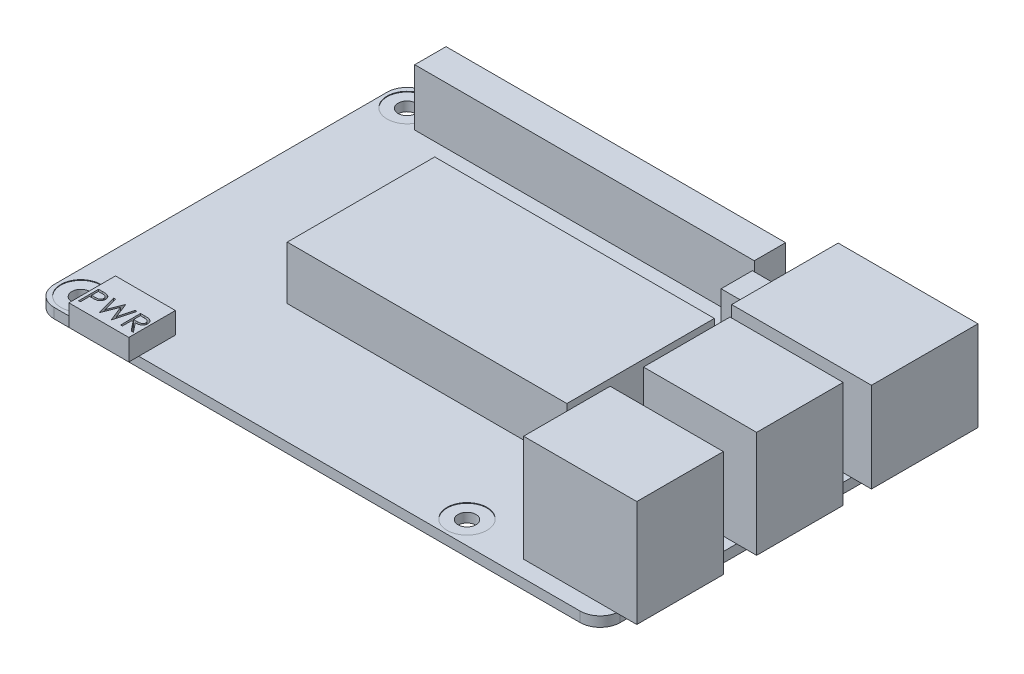
SolidWorks part; units mm, degrees
ref_plane "Front Plane" through (0, 0, 0) normal (0, 0, 1) x (1, 0, 0)
ref_plane "Top Plane" through (0, 0, 0) normal (0, 1, 0) x (1, 0, 0)
ref_plane "Right Plane" through (0, 0, 0) normal (1, 0, 0) x (0, 0, -1)
sketch "Sketch1" plane through (0, 0, 0) normal (0, 1, 0) x (1, 0, 0)
  line L0 (3.5, 52.5) -> (61.5, 52.5) construction
  line L1 (0, 0) -> (85, 0)
  line L2 (0, 0) -> (0, 56)
  line L3 (0, 56) -> (85, 56)
  line L4 (85, 0) -> (85, 56)
  line L5 (61.5, 52.5) -> (61.5, 3.5) construction
  line L6 (61.5, 3.5) -> (3.5, 3.5) construction
  line L7 (3.5, 3.5) -> (3.5, 52.5) construction
  circle A0 centre (3.5, 52.5) radius 1.35
  circle A1 centre (3.5, 3.5) radius 1.35
  circle A2 centre (61.5, 3.5) radius 1.35
  circle A3 centre (61.5, 52.5) radius 1.35
  dimension "D5" = 2.7
  dimension "D6" = 3.5
  dimension "D7" = 3.5
  dimension "D1" = 85
  dimension "D2" = 56
  dimension "D3" = 58
  dimension "D4" = 49
extrude "Boss-Extrude1" add sketch "Sketch1" along normal blind 1.5
fillet "Fillet1" radius 3 4 edges at (85, 0.75, -56) (85, 0.75, 0) (0, 0.75, -56) (0, 0.75, 0)
sketch "Sketch2" plane through (0, 1.5, 0) normal (0, 1, 0) x (1, 0, 0)
  line L0 (3, 0) -> (82, 0) construction
  line L1 (88, 20.5) -> (71, 20.5)
  line L2 (88, 20.5) -> (88, 33.5)
  line L3 (88, 33.5) -> (71, 33.5)
  line L4 (71, 20.5) -> (71, 33.5)
  line L5 (88, 2.5) -> (71, 2.5)
  line L6 (88, 2.5) -> (88, 15.5)
  line L7 (88, 15.5) -> (71, 15.5)
  line L8 (71, 2.5) -> (71, 15.5)
  line L9 (85, 3) -> (85, 53) construction
  point P8 (88, 9)
  point P11 (88, 27)
  dimension "D1" = 17
  dimension "D2" = 13
  dimension "D3" = 9
  dimension "D4" = 27
  dimension "D5" = 3
extrude "Boss-Extrude2" add sketch "Sketch2" along normal blind 16
sketch "Sketch3" plane through (0, 1.5, 0) normal (0, 1, 0) x (1, 0, 0)
  line L0 (88, 20.5) -> (88, 33.5) construction
  line L1 (88, 37.75) -> (67, 37.75)
  line L2 (88, 37.75) -> (88, 53.75)
  line L3 (88, 53.75) -> (67, 53.75)
  line L4 (67, 37.75) -> (67, 53.75)
  line L5 (3, 0) -> (82, 0) construction
  point P6 (88, 45.75)
  dimension "D1" = 21
  dimension "D2" = 16
  dimension "D3" = 45.75
extrude "Boss-Extrude3" add sketch "Sketch3" along normal blind 13.5
sketch "Sketch4" plane through (0, 1.5, 0) normal (0, 1, 0) x (1, 0, 0)
  line L0 (61.5, 52.5) -> (61.5, 48.71) construction
  line L1 (7, 54.85) -> (58, 54.85)
  line L2 (7, 54.85) -> (7, 50.15)
  line L3 (7, 50.15) -> (58, 50.15)
  line L4 (58, 54.85) -> (58, 50.15)
  line L5 (59.15, 48.71) -> (63.85, 48.71)
  line L6 (59.15, 48.71) -> (59.15, 44.01)
  line L7 (59.15, 44.01) -> (63.85, 44.01)
  line L8 (63.85, 48.71) -> (63.85, 44.01)
  line L9 (3.5, 52.5) -> (61.5, 52.5) construction
  point P11 (63.85, 46.36)
  point P13 (32.5, 52.5)
  point P15 (32.5, 54.85)
  point P16 (7, 52.5)
  dimension "D1" = 6.14
  dimension "D2" = 51
  dimension "D3" = 4.7
  dimension "D4" = 4.7
extrude "Boss-Extrude4" add sketch "Sketch4" along normal blind 8.5
sketch "Sketch5" plane through (0, 1.5, 0) normal (0, 1, 0) x (1, 0, 0)
  line L0 (3, 0) -> (82, 0) construction
  line L1 (6.7, -1.5) -> (15.7, -1.5)
  line L2 (6.7, -1.5) -> (6.7, 5.5)
  line L3 (6.7, 5.5) -> (15.7, 5.5)
  line L4 (15.7, -1.5) -> (15.7, 5.5)
  circle A0 centre (3.5, 3.5) radius 1.35 construction
  point P8 (11.2, -1.5)
  dimension "D4" = 7.7
  dimension "D1" = 9
  dimension "D2" = 7
  dimension "D3" = 1.5
extrude "Boss-Extrude5" add sketch "Sketch5" along normal blind 3.2
sketch "Sketch6" plane through (0, 4.7, 0) normal (0, 1, 0) x (1, 0, 0)
  line L0 (6.7, -0.5) -> (15.7, -0.5) construction
  line L1 (6.7, 5.5) -> (6.7, -1.5) construction
  line L2 (15.7, -1.5) -> (15.7, 5.5) construction
  line L3 (6.7, -1.5) -> (15.7, -1.5) construction
  text T0 "PWR" font "Century Gothic" height 3
  dimension "D1" = 1
extrude "Cut-Extrude1" cut sketch "Sketch6" against normal blind 1
sketch "Sketch7" plane through (0, 1.5, 0) normal (0, 1, 0) x (1, 0, 0)
  line L0 (0, 53) -> (0, 3) construction
  line L5 (62, 18) -> (20, 18)
  line L6 (62, 18) -> (62, 40.15)
  line L7 (62, 40.15) -> (20, 40.15)
  line L8 (20, 18) -> (20, 40.15)
  line L9 (67, 53.75) -> (67, 37.75) construction
  line L10 (7, 50.15) -> (58, 50.15) construction
  line L11 (15.7, 0) -> (82, 0) construction
  point P0 (14.4381, 36.9872)
  dimension "D1" = 20
  dimension "D2" = 5
  dimension "D3" = 10
  dimension "D4" = 18
extrude "Boss-Extrude6" add sketch "Sketch7" along normal blind 8
sketch "Sketch8" plane through (0, 10, 0) normal (0, 1, 0) x (1, 0, 0)
  line L0 (7, 52.5) -> (58, 52.5)
  line L1 (7, 54.85) -> (7, 50.15) construction
  line L2 (58, 50.15) -> (58, 54.85) construction
  line L3 (9.5, 54.85) -> (9.5, 50.15)
  line L4 (7, 54.85) -> (58, 54.85)
  line L5 (7, 54.85) -> (7, 50.15)
  line L6 (7, 50.15) -> (58, 50.15)
  line L7 (58, 54.85) -> (58, 50.15)
  line L8 (12, 54.85) -> (12, 50.15)
  line L9 (14.5, 54.85) -> (14.5, 50.15)
  line L10 (17, 54.85) -> (17, 50.15)
  line L11 (19.5, 54.85) -> (19.5, 50.15)
  line L12 (22, 54.85) -> (22, 50.15)
  line L13 (24.5, 54.85) -> (24.5, 50.15)
  line L14 (27, 54.85) -> (27, 50.15)
  line L15 (29.5, 54.85) -> (29.5, 50.15)
  line L16 (32, 54.85) -> (32, 50.15)
  line L17 (34.5, 54.85) -> (34.5, 50.15)
  line L18 (37, 54.85) -> (37, 50.15)
  line L19 (39.5, 54.85) -> (39.5, 50.15)
  line L20 (42, 54.85) -> (42, 50.15)
  line L21 (44.5, 54.85) -> (44.5, 50.15)
  line L22 (47, 54.85) -> (47, 50.15)
  line L23 (49.5, 54.85) -> (49.5, 50.15)
  line L24 (52, 54.85) -> (52, 50.15)
  line L25 (54.5, 54.85) -> (54.5, 50.15)
  line L26 (9.5, 54.85) -> (12, 54.85) construction
  text T0 " 5V   5V                 TX   RX" font "Century Gothic" height 1
  text T1 "3V3                                                  3V3" font "Century Gothic" height 1
  dimension "D1" = 51
  dimension "D2" = 2.5
  dimension "D4" = 2.5
  dimension "D3" = 19
sketch "Sketch9" plane through (0, 1.5, 0) normal (0, 1, 0) x (1, 0, 0)
  circle A0 centre (3.5, 52.5) radius 3
  circle A1 centre (3.5, 3.5) radius 3
  circle A2 centre (61.5, 52.5) radius 3
  circle A3 centre (61.5, 3.5) radius 3
  dimension "D1" = 6
extrude "Cut-Extrude2" cut sketch "Sketch9" against normal blind 0.1
equation "\"D2@Sketch8\"=\"D1@Sketch8\"/20"
equation "\"D4@Sketch8\"=\"D2@Sketch8\""
